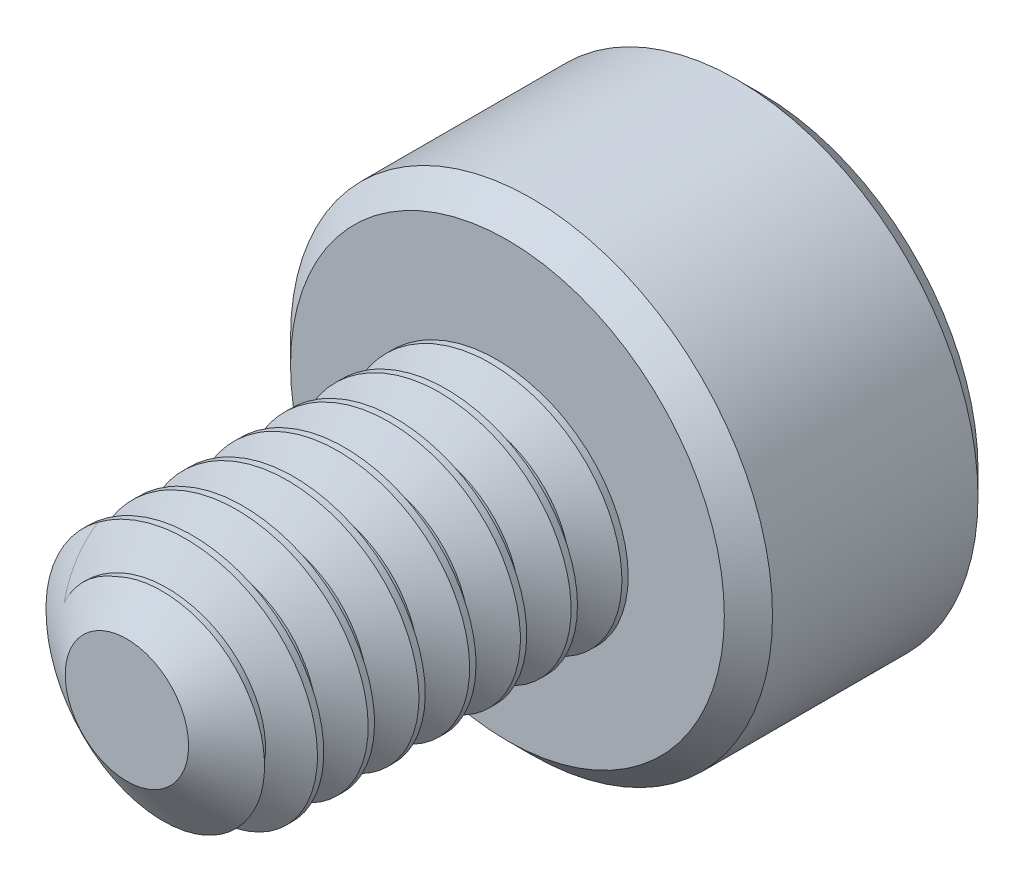
SolidWorks part; units mm, degrees
other "DetailItem1"
ref_plane "Front Plane" through (0, 0, 0) normal (0, 0, 1) x (1, 0, 0)
ref_plane "Top Plane" through (0, 0, 0) normal (0, 1, 0) x (1, 0, 0)
ref_plane "Right Plane" through (0, 0, 0) normal (1, 0, 0) x (0, 0, -1)
sketch "Sketch1" plane through (0, 0, 0) normal (0, 0, 1) x (1, 0, 0)
  circle A0 centre (0, 0) radius 1
  dimension "OD" = 2
extrude "Extrude1" add sketch "Sketch1" against normal blind 3
sketch "Sketch2" plane through (0, 0, 0) normal (0, 0, 1) x (1, 0, 0)
  circle A0 centre (0, 0) radius 1 construction
  circle A1 centre (0, 0) radius 1
curve "Helix/Spiral1" pitch 0.4 height 3.4 radius 1 centre (0, 0, 0) axis (0, 0, -1) start towards (0, 1, 0) parameters "pitch"=0.4
sketch "Sketch3" plane through (0, 0, 0) normal (1, 0, 0) x (0, 0, -1)
  line L0 (-0.35, 1) -> (-0.2, 0.7402)
  line L1 (-0.2, 0.7402) -> (-0.15, 0.7402)
  line L2 (-0.15, 0.7402) -> (0, 1)
  line L3 (-0.35, 1) -> (0, 1)
  line L4 (-0.175, 1) -> (-0.175, 0.7402) construction
  line L5 (-0.275, 0.8701) -> (-0.075, 0.8701) construction
  line L6 (0, 1) -> (0, -1) construction
  dimension "D1" = 0.05
  dimension "D2" = 0.2
  dimension "D3" = 60
sweep "Cut-Sweep1" cut profiles "Sketch3" path "Helix/Spiral1"
sketch "Sketch4" plane through (0, 0, 0) normal (1, 0, 0) x (0, 0, -1)
  line L0 (0.3598, 1) -> (0, 0.4862)
  line L1 (0, 0.4862) -> (0, 1)
  line L2 (0.3598, 1) -> (0, 1)
  line L3 (-0.35, 1) -> (0, 1) construction
  line L4 (0, 0) -> (7.0209, 0) construction
  dimension "D1" = 55
  dimension "D2" = 0.254
revolve "Cut-Revolve1" cut sketch "Sketch4" angle 360 about L4
sketch "Sketch6" plane through (0, 0, -3) normal (0, 0, -1) x (-1, 0, 0)
  circle A0 centre (0, 0) radius 1.9
  dimension "head dia" = 3.8
extrude "Extrude2" add sketch "Sketch6" along normal blind 2
sketch "Sketch7" plane through (0, 0, -5) normal (0, 0, -1) x (-1, 0, 0)
  line L1 (0, 0.866) -> (-0.75, 0.433)
  line L2 (-0.75, 0.433) -> (-0.75, -0.433)
  line L3 (-0.75, -0.433) -> (0, -0.866)
  line L4 (0, -0.866) -> (0.75, -0.433)
  line L5 (0.75, -0.433) -> (0.75, 0.433)
  line L6 (0.75, 0.433) -> (0, 0.866)
  circle A0 centre (0, 0) radius 0.75 construction
  dimension "hex dia" = 1.5
extrude "Cut-Extrude1" cut sketch "Sketch7" against normal blind 1.125
sketch "Sketch8" plane through (0, 0, -5) normal (0, 0, -1) x (-1, 0, 0)
  circle A0 centre (0, 0) radius 0.866
extrude "Cut-Extrude2" cut sketch "Sketch8" against normal through all draft 45
chamfer "Chamfer1" distance 0.19 angle 45 2 edges at (-1.9, 0, -5) (-1.9, 0, -3)
sketch "Sketch10" plane through (0, 0, -3) normal (0, 0, 1) x (1, 0, 0)
  circle A1 centre (0, 0) radius 1
  circle A2 centre (0, 0) radius 1
  dimension "D1" = 0
ref_plane "Plane1" through (0, 0, 0) normal (0, 0, 1) x (1, 0, 0)
extrude "partial thread" [suppressed] add sketch "Sketch10" along normal up to surface (2 mm away) separate body up to plane "Plane1"
chamfer "Chamfer2" [suppressed] distance 0.04 angle 45
combine bodies "Combine1" [suppressed] operation type add bodies to combine 107 108
sketch "Sketch9" plane through (0, 0, 0) normal (1, 0, 0) x (0, 0, -1)
  line L0 (0, 1) -> (0, -1) construction
  line L1 (1, 1) -> (1, -1) construction
  dimension "D1" = 1
equation "\"D3@Helix/Spiral1\" = \"screw length@Extrude1\"+\"pitch@Helix/Spiral1\""
equation "\"D1@Sketch3\" = \"pitch@Helix/Spiral1\"*.125"
equation "\"D2@Sketch3\" = \"pitch@Helix/Spiral1\"*.5"
equation "\"D1@Cut-Extrude1\" = \"hex dia@Sketch7\"*.75"
equation "\"D1@Chamfer1\" = \"head dia@Sketch6\"*.05"
equation "\"D1@Sketch9\" = \"pitch@Helix/Spiral1\"*2.5"
equation "\"D1@Chamfer2\"=\"OD@Sketch1\"*.02"
